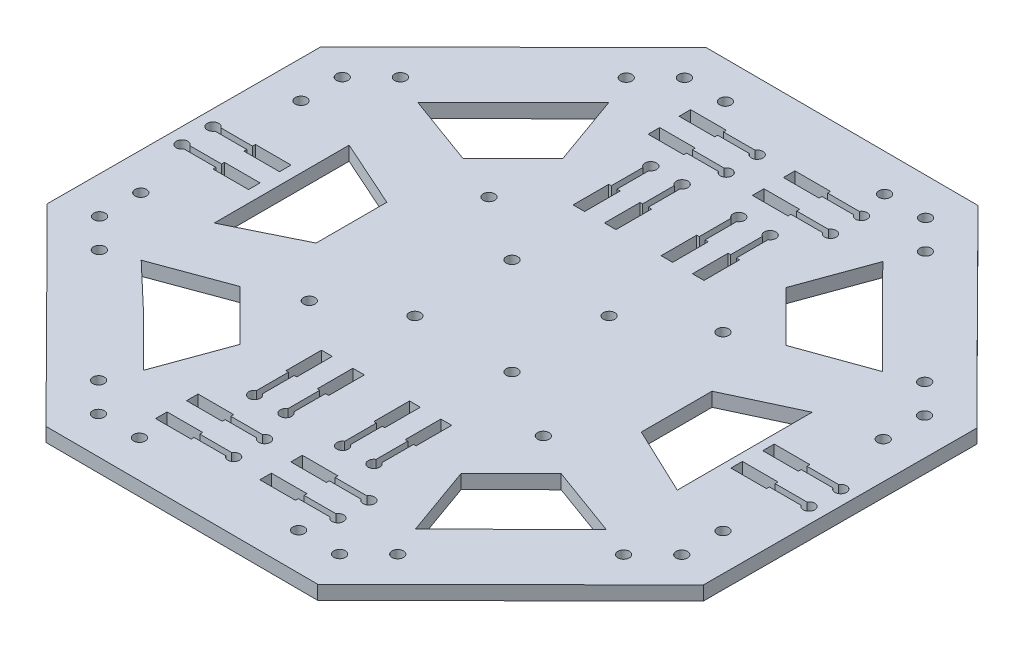
SolidWorks part; units mm, degrees
ref_plane "Front Plane" through (0, 0, 0) normal (0, 0, 1) x (1, 0, 0)
ref_plane "Top Plane" through (0, 0, 0) normal (0, 1, 0) x (1, 0, 0)
ref_plane "Right Plane" through (0, 0, 0) normal (1, 0, 0) x (0, 0, -1)
sketch "Sketch1" plane through (0, 0, 0) normal (0, 1, 0) x (1, 0, 0)
  line L1 (-101.7349, -41.757) -> (-42.4107, -101.4641)
  line L2 (-42.4107, -101.4641) -> (41.757, -101.7349)
  line L3 (41.757, -101.7349) -> (101.4641, -42.4107)
  line L4 (101.4641, -42.4107) -> (101.7349, 41.757)
  line L5 (101.7349, 41.757) -> (42.4107, 101.4641)
  line L6 (42.4107, 101.4641) -> (-41.757, 101.7349)
  line L7 (-41.757, 101.7349) -> (-101.4641, 42.4107)
  line L8 (-101.4641, 42.4107) -> (-101.7349, -41.757)
  circle A0 centre (0, 0) radius 101.6 construction
extrude "Boss-Extrude1" add sketch "Sketch1" along normal blind 4.318
sketch "Sketch6" plane through (0, 4.318, 0) normal (0, 1, 0) x (1, 0, 0)
  line L3 (-71.639, 42.551) -> (-56.8641, 57.2312)
  line L4 (-42.0892, 71.9113) -> (-56.8641, 57.2312)
  line L5 (71.639, -42.551) -> (56.8641, -57.2312)
  line L6 (42.0892, -71.9113) -> (56.8641, -57.2312)
  line L10 (42.6973, 71.7844) -> (57.3775, 57.0095)
  line L11 (72.0884, 42.3305) -> (57.3775, 57.0095)
  line L12 (-42.3683, -71.4575) -> (-57.0485, -56.6826)
  line L13 (-72.1494, -42.338) -> (-57.0485, -56.6826)
  line L17 (72.0884, -0.2319) -> (72.0884, 20.5959)
  line L18 (72.0884, -0.2319) -> (72.0884, -21.0601)
  line L19 (-70.8099, 20.5255) -> (-70.8099, -21.1305)
  line L20 (-42.0049, 42.276) -> (-34.2571, 49.9742)
  line L21 (-42.0049, 42.276) -> (-49.7279, 34.553)
  line L22 (-49.7279, 0.16) -> (-49.7279, 11.082)
  line L23 (-49.7279, 0.16) -> (-49.7279, -10.762)
  line L24 (-42.0934, -41.8234) -> (-34.3704, -49.5464)
  line L25 (-42.0934, -41.8234) -> (-49.8164, -34.1004)
  line L26 (42.0049, -42.276) -> (49.7527, -34.5779)
  line L27 (51.0064, -0.1641) -> (51.0064, -11.0861)
  line L28 (42.4224, 42.1503) -> (34.7242, 49.8981)
  line L29 (42.4224, 42.1503) -> (50.1205, 34.4024)
  line L30 (51.0064, -0.1641) -> (51.0064, 10.7579)
  line L31 (42.0049, -42.276) -> (34.2571, -49.9742)
  line L32 (-42.0892, 71.9113) -> (-34.2571, 49.9742)
  line L33 (-71.639, 42.551) -> (-49.7279, 34.553)
  line L34 (-70.8099, 20.5255) -> (-49.7279, 11.082)
  line L35 (-70.8099, -21.1305) -> (-49.7279, -10.762)
  line L36 (-49.8164, -34.1004) -> (-72.1494, -42.338)
  line L37 (-34.3704, -49.5464) -> (-42.3683, -71.4575)
  line L38 (42.0892, -71.9113) -> (34.2571, -49.9742)
  line L39 (71.639, -42.551) -> (49.7527, -34.5779)
  line L40 (72.0884, -21.0601) -> (51.0064, -11.0861)
  line L41 (51.0064, 10.7579) -> (72.0884, 20.5959)
  line L42 (72.0884, 42.3305) -> (50.1205, 34.4024)
  line L43 (34.7242, 49.8981) -> (42.6973, 71.7844)
  point P14 (-38.4006, -92.086)
  point P15 (38.0534, -92.3317)
  point P17 (38.4489, 92.2928)
  point P24 (-38.0051, 92.4948)
  point P25 (-92.3358, -37.8992)
  point P26 (-92.1872, 38.5548)
  point P27 (92.4109, 38.1328)
  point P28 (92.1652, -38.3212)
  point P40 (-42.0934, -41.8234)
  dimension "D3" = 76.454
  dimension "D4" = 76.454
  dimension "D9" = 76.454
  dimension "D12" = 76.454
  dimension "D15" = 76.454
  dimension "D18" = 76.454
  dimension "D20" = 76.454
  dimension "D21" = 76.454
extrude "Cut-Extrude1" cut sketch "Sketch6" against normal blind 12.7
ref_plane "Plane1" through (101.4641, 4.318, 42.4107) normal (0.7094, 0, -0.7048) x (-0.7048, 0, -0.7094)
hole_wizard "#15 (0.14) Diameter Hole1" positions "3DSketch3" profile "Sketch14" hole size "#15" standard "ANSI Inch" end condition through all
sketch3d "3DSketch3"
  line L0 (-42.4107, 4.318, 101.4641) -> (41.757, 4.318, 101.7349) construction
  line L1 (41.757, 4.318, 101.7349) -> (101.4641, 4.318, 42.4107) construction
  line L2 (101.4641, 4.318, 42.4107) -> (101.7349, 4.318, -41.757) construction
  line L3 (101.7349, 4.318, -41.757) -> (42.4107, 4.318, -101.4641) construction
  line L4 (42.4107, 4.318, -101.4641) -> (-41.757, 4.318, -101.7349) construction
  line L5 (-41.757, 4.318, -101.7349) -> (-101.4641, 4.318, -42.4107) construction
  line L6 (-101.4641, 4.318, -42.4107) -> (-101.7349, 4.318, 41.757) construction
  line L7 (-101.7349, 4.318, 41.757) -> (-42.4107, 4.318, 101.4641) construction
  point P0 (-37.6395, 4.318, 90.0494)
  point P2 (37.0594, 4.318, 90.2897)
  point P4 (90.0494, 4.318, 37.6395)
  point P6 (90.2897, 4.318, -37.0594)
  point P8 (37.6395, 4.318, -90.0494)
  point P10 (-37.0594, 4.318, -90.2897)
  point P12 (-90.0494, 4.318, -37.6395)
  point P14 (-90.2897, 4.318, 37.0594)
  dimension "D1" = 11.43
  dimension "D3" = 11.43
  dimension "D2" = 11.43
  dimension "D4" = 11.43
  dimension "D5" = 11.43
  dimension "D6" = 11.43
  dimension "D7" = 11.43
  dimension "D8" = 11.43
  dimension "D9" = 11.43
  dimension "D10" = 11.43
  dimension "D11" = 11.43
  dimension "D12" = 11.43
  dimension "D13" = 11.43
  dimension "D14" = 11.43
  dimension "D15" = 11.43
  dimension "D16" = 11.43
sketch "Sketch14" plane through (-37.6395, 4.318, 90.0494) normal (1, 0, 0) x (0, 0, 1)
  line L0 (0, 0) -> (0, 4.318)
  line L1 (0, 4.318) -> (1.778, 4.318)
  line L2 (1.778, 4.318) -> (1.778, 0)
  line L5 (1.778, 0) -> (0, 0)
  line L11 (0, -6.35) -> (0, 107.95) construction
  dimension "Thru Hole Dia." = 3.556
  dimension "Thru Hole Depth" = 4.318
sketch3d "3DSketch4"
  point P0 (10.0148, 4.318, 38.2045)
ref_plane "Plane2" through (0, 4.318, 0) normal (0, 1, 0) x (1, 0, 0)
sketch "Sketch19" plane through (0, 4.318, 0) normal (0, 1, 0) x (1, 0, 0)
  line L9 (-101.4641, 42.4107) -> (-101.7349, -41.757) construction
  line L10 (-101.7349, -41.757) -> (-42.4107, -101.4641) construction
  line L11 (-42.4107, -101.4641) -> (41.757, -101.7349) construction
  line L12 (41.757, -101.7349) -> (101.4641, -42.4107) construction
  line L13 (101.4641, -42.4107) -> (101.7349, 41.757) construction
  line L14 (101.7349, 41.757) -> (42.4107, 101.4641) construction
  line L15 (42.4107, 101.4641) -> (-41.757, 101.7349) construction
  line L16 (-41.757, 101.7349) -> (-101.4641, 42.4107) construction
  circle A8 centre (-90.0494, 37.6395) radius 1.778 construction
  circle A9 centre (-90.2897, -37.0594) radius 1.778 construction
  circle A10 centre (-37.6395, -90.0494) radius 1.778 construction
  circle A11 centre (37.0594, -90.2897) radius 1.778 construction
  circle A12 centre (90.0494, -37.6395) radius 1.778 construction
  circle A13 centre (90.2897, 37.0594) radius 1.778 construction
  circle A14 centre (37.6395, 90.0494) radius 1.778 construction
  circle A15 centre (-37.0594, 90.2897) radius 1.778 construction
  point P1 (-90.2488, -24.3594)
  point P2 (-90.0902, 24.9395)
  point P10 (-81.3384, -46.0685)
  point P11 (-46.5908, -81.0403)
  point P12 (-24.9395, -90.0902)
  point P13 (24.3594, -90.2488)
  point P14 (46.0685, -81.3384)
  point P15 (81.0403, -46.5908)
  point P16 (90.0902, -24.9395)
  point P17 (90.2488, 24.3594)
  point P18 (81.3384, 46.0685)
  point P19 (46.5908, 81.0403)
  point P20 (24.9395, 90.0902)
  point P21 (-24.3594, 90.2488)
  point P22 (-81.0403, 46.5908)
  point P23 (-46.0685, 81.3384)
  dimension "D2" = 11.43
  dimension "D7" = 12.7
  dimension "D11" = 11.43
  dimension "D13" = 12.7
  dimension "D16" = 11.43
  dimension "D3" = 12.7
  dimension "D5" = 12.7
  dimension "D10" = 12.7
  dimension "D12" = 12.7
  dimension "D20" = 12.7
  dimension "D27" = 12.7
  dimension "D30" = 12.7
  dimension "D1" = 12.7
  dimension "D4" = 11.43
  dimension "D6" = 11.43
  dimension "D8" = 11.43
  dimension "D9" = 11.43
  dimension "D14" = 11.43
  dimension "D15" = 12.7
  dimension "D17" = 12.7
  dimension "D18" = 11.43
  dimension "D19" = 11.43
  dimension "D21" = 12.7
  dimension "D22" = 11.43
  dimension "D23" = 12.7
  dimension "D24" = 11.43
  dimension "D25" = 12.7
  dimension "D26" = 11.43
  dimension "D28" = 11.43
  dimension "D29" = 11.43
  dimension "D31" = 12.7
  dimension "D32" = 11.43
hole_wizard "#15 (0.14) Diameter Hole3" positions "3DSketch5" profile "Sketch20" hole size "#15" standard "ANSI Inch" end condition through all
sketch3d "3DSketch5"
  point P0 (-90.2488, 4.318, 24.3594)
  point P3 (-81.3384, 4.318, 46.0685)
  point P6 (-46.5908, 4.318, 81.0403)
  point P9 (-24.9395, 4.318, 90.0902)
  point P12 (24.3594, 4.318, 90.2488)
  point P15 (46.0685, 4.318, 81.3384)
  point P18 (81.0403, 4.318, 46.5908)
  point P21 (90.0902, 4.318, 24.9395)
  point P24 (90.2488, 4.318, -24.3594)
  point P27 (81.3384, 4.318, -46.0685)
  point P30 (46.5908, 4.318, -81.0403)
  point P33 (24.9395, 4.318, -90.0902)
  point P36 (-24.3594, 4.318, -90.2488)
  point P39 (-46.0685, 4.318, -81.3384)
  point P42 (-81.0403, 4.318, -46.5908)
  point P45 (-90.0902, 4.318, -24.9395)
sketch "Sketch20" plane through (-90.2488, 4.318, 24.3594) normal (1, 0, 0) x (0, 0, 1)
  line L0 (0, 0) -> (0, 4.318)
  line L1 (0, 4.318) -> (1.778, 4.318)
  line L2 (1.778, 4.318) -> (1.778, 0)
  line L5 (1.778, 0) -> (0, 0)
  line L11 (0, -6.35) -> (0, 107.95) construction
  dimension "Thru Hole Dia." = 3.556
  dimension "Thru Hole Depth" = 4.318
sketch "Sketch21" plane through (0, 4.318, 0) normal (0, 1, 0) x (1, 0, 0)
  point P1 (-14.986, 14.986)
  point P3 (14.986, 14.986)
  point P4 (14.986, -14.986)
  point P7 (-14.986, -14.986)
hole_wizard "#15 (0.14) Diameter Hole4" positions "3DSketch6" profile "Sketch22" hole size "#15" standard "ANSI Inch" end condition through all
sketch3d "3DSketch6"
  point P0 (-14.986, 4.318, -14.986)
  point P3 (14.986, 4.318, -14.986)
  point P6 (14.986, 4.318, 14.986)
  point P9 (-14.986, 4.318, 14.986)
sketch "Sketch22" plane through (-14.986, 4.318, -14.986) normal (1, 0, 0) x (0, 0, 1)
  line L0 (0, 0) -> (0, 4.318)
  line L1 (0, 4.318) -> (1.778, 4.318)
  line L2 (1.778, 4.318) -> (1.778, 0)
  line L5 (1.778, 0) -> (0, 0)
  line L11 (0, -6.35) -> (0, 107.95) construction
  dimension "Thru Hole Dia." = 3.556
  dimension "Thru Hole Depth" = 4.318
sketch "Sketch23" plane through (0, 4.318, 0) normal (0, 1, 0) x (1, 0, 0)
  point P0 (-35.3353, 28.2247)
  point P1 (36.9126, 28.2247)
  point P2 (36.9126, -27.2465)
  point P3 (-35.3353, -27.2465)
hole_wizard "#15 (0.14) Diameter Hole5" positions "3DSketch7" profile "Sketch24" hole size "#15" standard "ANSI Inch" end condition through all
sketch3d "3DSketch7"
  point P0 (-35.3353, 4.318, -28.2247)
  point P3 (-35.3353, 4.318, 27.2465)
  point P6 (36.9126, 4.318, 27.2465)
  point P9 (36.9126, 4.318, -28.2247)
sketch "Sketch24" plane through (-35.3353, 4.318, -28.2247) normal (1, 0, 0) x (0, 0, 1)
  line L0 (0, 0) -> (0, 4.318)
  line L1 (0, 4.318) -> (1.778, 4.318)
  line L2 (1.778, 4.318) -> (1.778, 0)
  line L5 (1.778, 0) -> (0, 0)
  line L11 (0, -6.35) -> (0, 107.95) construction
  dimension "Thru Hole Dia." = 3.556
  dimension "Thru Hole Depth" = 4.318
sketch "Sketch26" plane through (0, 4.318, 0) normal (0, 1, 0) x (1, 0, 0)
  line L16 (-10.5804, -38.5558) -> (-10.5804, -49.5558)
  line L17 (-10.5804, -49.5558) -> (-9.8004, -49.5558)
  line L20 (-8.02, -49.5558) -> (-7.02, -49.5558)
  line L21 (-7.02, -49.5558) -> (-7.02, -38.5558)
  line L22 (-7.02, -38.5558) -> (-10.5804, -38.5558)
  line L23 (-9.8004, -49.5558) -> (-9.8004, -59.3344)
  line L24 (-8.02, -49.5558) -> (-8.02, -59.3344)
  line L25 (-20.2604, -38.5558) -> (-20.2604, -49.5558)
  line L26 (-20.2604, -49.5558) -> (-19.4804, -49.5558)
  line L27 (-17.7, -49.5558) -> (-16.92, -49.5558)
  line L28 (-16.92, -49.5558) -> (-16.92, -38.5558)
  line L29 (-16.92, -38.5558) -> (-20.2604, -38.5558)
  line L30 (-19.4804, -49.5558) -> (-19.4804, -59.3344)
  line L31 (-17.7, -49.5558) -> (-17.7, -59.3344)
  line L32 (16.5913, -38.5558) -> (16.5913, -49.5558)
  line L33 (16.5913, -49.5558) -> (17.3713, -49.5558)
  line L34 (19.1517, -49.5558) -> (19.9317, -49.5558)
  line L35 (19.9317, -49.5558) -> (19.9317, -38.5558)
  line L36 (19.9317, -38.5558) -> (16.5913, -38.5558)
  line L37 (17.3713, -49.5558) -> (17.3713, -59.3344)
  line L38 (19.1517, -49.5558) -> (19.1517, -59.3344)
  line L39 (6.9116, -38.5558) -> (6.9116, -49.5558)
  line L40 (6.9116, -49.5558) -> (7.6916, -49.5558)
  line L41 (9.472, -49.5558) -> (10.252, -49.5558)
  line L42 (10.252, -49.5558) -> (10.252, -38.5558)
  line L43 (10.252, -38.5558) -> (6.9116, -38.5558)
  line L44 (7.6916, -49.5558) -> (7.6916, -59.3344)
  line L45 (9.472, -49.5558) -> (9.472, -59.3344)
  line L60 (10.4713, 39.1249) -> (10.4713, 50.1249)
  line L61 (10.4713, 50.1249) -> (9.4717, 50.1249)
  line L62 (7.6913, 50.1249) -> (6.9113, 50.1249)
  line L63 (6.9113, 50.1249) -> (6.9113, 39.1249)
  line L64 (6.9113, 39.1249) -> (10.4713, 39.1249)
  line L65 (9.4717, 50.1249) -> (9.4717, 59.9035)
  line L66 (7.6913, 50.1249) -> (7.6913, 59.9035)
  line L67 (20.1513, 39.1249) -> (20.1513, 50.1249)
  line L68 (20.1513, 50.1249) -> (19.1517, 50.1249)
  line L69 (17.3713, 50.1249) -> (16.5913, 50.1249)
  line L70 (16.5913, 50.1249) -> (16.5913, 39.1249)
  line L71 (16.5913, 39.1249) -> (20.1513, 39.1249)
  line L72 (19.1517, 50.1249) -> (19.1517, 59.9035)
  line L73 (17.3713, 50.1249) -> (17.3713, 59.9035)
  line L74 (-16.7004, 39.1249) -> (-16.7004, 50.1249)
  line L75 (-16.7004, 50.1249) -> (-17.7, 50.1249)
  line L76 (-19.4804, 50.1249) -> (-20.2604, 50.1249)
  line L77 (-20.2604, 50.1249) -> (-20.2604, 39.1249)
  line L78 (-20.2604, 39.1249) -> (-16.7004, 39.1249)
  line L79 (-17.7, 50.1249) -> (-17.7, 59.9035)
  line L80 (-19.4804, 50.1249) -> (-19.4804, 59.9035)
  line L81 (-7.0207, 39.1249) -> (-7.0207, 50.1249)
  line L82 (-7.0207, 50.1249) -> (-8.0203, 50.1249)
  line L83 (-9.8007, 50.1249) -> (-10.5807, 50.1249)
  line L84 (-10.5807, 50.1249) -> (-10.5807, 39.1249)
  line L85 (-10.5807, 39.1249) -> (-7.0207, 39.1249)
  line L86 (-8.0203, 50.1249) -> (-8.0203, 59.9035)
  line L87 (-9.8007, 50.1249) -> (-9.8007, 59.9035)
  arc A2 (-9.8004, -59.3344) -> (-8.02, -59.3344) centre (-8.9102, -60.8758) ccw
  arc A3 (-19.4804, -59.3344) -> (-17.7, -59.3344) centre (-18.5902, -60.8758) ccw
  arc A4 (17.3713, -59.3344) -> (19.1517, -59.3344) centre (18.2615, -60.8758) ccw
  arc A5 (7.6916, -59.3344) -> (9.472, -59.3344) centre (8.5818, -60.8758) ccw
  arc A8 (9.4717, 59.9035) -> (7.6913, 59.9035) centre (8.5815, 61.4449) ccw
  arc A9 (19.1517, 59.9035) -> (17.3713, 59.9035) centre (18.2615, 61.4449) ccw
  arc A10 (-17.7, 59.9035) -> (-19.4804, 59.9035) centre (-18.5902, 61.4449) ccw
  arc A11 (-8.0203, 59.9035) -> (-9.8007, 59.9035) centre (-8.9105, 61.4449) ccw
  point P54 (-18.4804, 39.1249)
  dimension "D4" = 62.61
  dimension "D2" = 62.61
  dimension "D3" = 62.61
  dimension "D5" = 1.78
  dimension "D6" = 1.78
  dimension "D7" = 1.78
  dimension "D8" = 1.78
  dimension "D9" = 1.78
  dimension "D10" = 1.78
  dimension "D11" = 1.78
  dimension "D12" = 1.78
  dimension "D1" = 62.61
  dimension "D13" = 0.78
  dimension "D14" = 0.78
  dimension "D15" = 0.78
  dimension "D16" = 11
  dimension "D17" = 11
  dimension "D18" = 11.32
  dimension "D19" = 11
  dimension "D20" = 11
  dimension "D21" = 11.32
  dimension "D22" = 0.78
  dimension "D23" = 11
  dimension "D24" = 11
  dimension "D25" = 11.32
  dimension "D26" = 11
  dimension "D27" = 11
  dimension "D28" = 11.32
  dimension "D29" = 11
  dimension "D30" = 11
  dimension "D31" = 11.32
  dimension "D32" = 11.32
  dimension "D33" = 11
  dimension "D34" = 11
  dimension "D35" = 11.32
  dimension "D36" = 11
  dimension "D37" = 11
  dimension "D38" = 11.32
  dimension "D39" = 11
  dimension "D40" = 11
  dimension "D41" = 62.9083
sketch "Sketch27" plane through (0, 4.318, 0) normal (0, 1, 0) x (1, 0, 0)
  line L0 (-27.5804, -72.9041) -> (-16.5804, -72.9041)
  line L1 (-16.5804, -72.9041) -> (-16.5804, -72.0145)
  line L2 (-16.5804, -70.2341) -> (-16.5804, -69.3441)
  line L3 (-16.5804, -69.3441) -> (-27.5804, -69.3441)
  line L4 (-27.5804, -69.3441) -> (-27.5804, -72.9041)
  line L5 (-16.5804, -72.0145) -> (-6.8018, -72.0145)
  line L6 (-16.5804, -70.2341) -> (-6.8018, -70.2341)
  line L7 (-27.5804, -82.4641) -> (-16.5804, -82.4641)
  line L8 (-16.5804, -82.4641) -> (-16.5804, -81.5745)
  line L9 (-16.5804, -79.7941) -> (-16.5804, -78.9041)
  line L10 (-16.5804, -78.9041) -> (-27.5804, -78.9041)
  line L11 (-27.5804, -78.9041) -> (-27.5804, -82.4641)
  line L12 (-16.5804, -81.5745) -> (-6.8018, -81.5745)
  line L13 (-16.5804, -79.7941) -> (-6.8018, -79.7941)
  line L14 (4.8856, -73.1749) -> (15.8856, -73.1749)
  line L15 (15.8856, -73.1749) -> (15.8856, -72.2853)
  line L16 (15.8856, -70.5049) -> (15.8856, -69.6149)
  line L17 (15.8856, -69.6149) -> (4.8856, -69.6149)
  line L18 (4.8856, -69.6149) -> (4.8856, -73.1749)
  line L19 (15.8856, -72.2853) -> (25.6642, -72.2853)
  line L20 (15.8856, -70.5049) -> (25.6642, -70.5049)
  line L21 (4.8807, -82.7349) -> (15.8807, -82.7349)
  line L22 (15.8807, -82.7349) -> (15.8807, -81.8453)
  line L23 (15.8807, -80.0649) -> (15.8807, -79.1749)
  line L24 (15.8807, -79.1749) -> (4.8807, -79.1749)
  line L25 (4.8807, -79.1749) -> (4.8807, -82.7349)
  line L26 (15.8807, -81.8453) -> (25.6593, -81.8453)
  line L27 (15.8807, -80.0649) -> (25.6593, -80.0649)
  line L28 (-74.4601, -3.3231) -> (-85.4601, -3.3231)
  line L57 (-85.4601, -3.3231) -> (-85.4601, -4.2131)
  line L58 (-85.4524, -5.9935) -> (-85.4524, -6.8835)
  line L59 (-27.5804, 79.1749) -> (-16.5804, 79.1749)
  line L60 (-16.5804, 79.1749) -> (-16.5804, 80.0645)
  line L61 (-16.5804, 81.8449) -> (-16.5804, 82.7349)
  line L62 (-16.5804, 82.7349) -> (-27.5804, 82.7349)
  line L63 (-27.5804, 82.7349) -> (-27.5804, 79.1749)
  line L64 (-16.5804, 80.0645) -> (-6.8018, 80.0645)
  line L65 (-16.5804, 81.8449) -> (-6.8018, 81.8449)
  line L66 (-27.5804, 69.6149) -> (-16.5804, 69.6149)
  line L67 (-16.5804, 69.6149) -> (-16.5804, 70.5045)
  line L68 (-16.5804, 72.2849) -> (-16.5804, 73.1749)
  line L69 (-16.5804, 73.1749) -> (-27.5804, 73.1749)
  line L70 (-27.5804, 73.1749) -> (-27.5804, 69.6149)
  line L71 (-16.5804, 70.5045) -> (-6.8018, 70.5045)
  line L72 (-16.5804, 72.2849) -> (-6.8018, 72.2849)
  line L73 (4.8856, 78.9041) -> (15.8856, 78.9041)
  line L74 (15.8856, 78.9041) -> (15.8856, 79.7937)
  line L75 (15.8856, 81.5741) -> (15.8856, 82.4641)
  line L76 (15.8856, 82.4641) -> (4.8856, 82.4641)
  line L77 (4.8856, 82.4641) -> (4.8856, 78.9041)
  line L78 (15.8856, 79.7937) -> (25.6642, 79.7937)
  line L79 (15.8856, 81.5741) -> (25.6642, 81.5741)
  line L80 (4.8807, 69.3441) -> (15.8807, 69.3441)
  line L81 (15.8807, 69.3441) -> (15.8807, 70.2337)
  line L82 (15.8807, 72.0141) -> (15.8807, 72.9041)
  line L83 (15.8807, 72.9041) -> (4.8807, 72.9041)
  line L84 (4.8807, 72.9041) -> (4.8807, 69.3441)
  line L85 (15.8807, 70.2337) -> (25.6593, 70.2337)
  line L86 (15.8807, 72.0141) -> (25.6593, 72.0141)
  line L87 (-85.4524, -6.8835) -> (-74.4601, -6.8835)
  line L88 (74.7349, 2.6743) -> (85.7349, 2.6743)
  line L89 (85.7349, 2.6743) -> (85.7349, 3.5616)
  line L90 (85.7349, 5.342) -> (85.7349, 6.232)
  line L91 (85.7349, 6.232) -> (74.7349, 6.232)
  line L92 (74.7349, 6.232) -> (74.7349, 2.6743)
  line L93 (85.7349, 3.5616) -> (95.5135, 3.5616)
  line L94 (85.7349, 5.342) -> (95.5135, 5.342)
  line L95 (74.4641, -6.8857) -> (85.4641, -6.8857)
  line L96 (85.4641, -6.8857) -> (85.4641, -5.9961)
  line L97 (85.4641, -4.2157) -> (85.4641, -3.3257)
  line L98 (85.4641, -3.3257) -> (74.4641, -3.3257)
  line L99 (74.4641, -3.3257) -> (74.4641, -6.8857)
  line L100 (85.4641, -5.9961) -> (95.2427, -5.9961)
  line L101 (85.4641, -4.2157) -> (95.2427, -4.2157)
  line L102 (-74.4601, -6.8835) -> (-74.4601, -3.3231)
  line L103 (-85.4601, -4.2131) -> (-95.2387, -4.2131)
  line L104 (-85.4524, -5.9935) -> (-95.2387, -5.9935)
  line L105 (-74.4524, 6.2347) -> (-85.4524, 6.2347)
  line L106 (-85.4524, 6.2347) -> (-85.4524, 5.3447)
  line L107 (-85.4524, 3.5643) -> (-85.4524, 2.6743)
  line L108 (-85.4524, 2.6743) -> (-74.4524, 2.6743)
  line L109 (-74.4524, 2.6743) -> (-74.4524, 6.2347)
  line L110 (-85.4524, 5.3447) -> (-95.2338, 5.3447)
  line L111 (-85.4524, 3.5643) -> (-95.2338, 3.5643)
  arc A0 (-6.8018, -72.0145) -> (-6.8018, -70.2341) centre (-5.2604, -71.1243) ccw
  arc A1 (-6.8018, -81.5745) -> (-6.8018, -79.7941) centre (-5.2604, -80.6843) ccw
  arc A2 (25.6642, -72.2853) -> (25.6642, -70.5049) centre (27.2056, -71.3951) ccw
  arc A3 (25.6593, -81.8453) -> (25.6593, -80.0649) centre (27.2007, -80.9551) ccw
  arc A8 (-6.8018, 80.0645) -> (-6.8018, 81.8449) centre (-5.2604, 80.9547) ccw
  arc A9 (-6.8018, 70.5045) -> (-6.8018, 72.2849) centre (-5.2604, 71.3947) ccw
  arc A10 (25.6642, 79.7937) -> (25.6642, 81.5741) centre (27.2056, 80.6839) ccw
  arc A11 (25.6593, 70.2337) -> (25.6593, 72.0141) centre (27.2007, 71.1239) ccw
  arc A12 (95.5135, 3.5616) -> (95.5135, 5.342) centre (97.0549, 4.4518) ccw
  arc A13 (95.2427, -5.9961) -> (95.2427, -4.2157) centre (96.7841, -5.1059) ccw
  arc A14 (-95.2387, -4.2131) -> (-95.2387, -5.9935) centre (-96.7801, -5.1033) ccw
  arc A15 (-95.2338, 5.3447) -> (-95.2338, 3.5643) centre (-96.7752, 4.4545) ccw
  point P133 (15.8807, 72.4591)
  point P134 (-16.5804, 72.7299)
  dimension "D4" = 1.78
  dimension "D2" = 1.78
  dimension "D3" = 1.78
  dimension "D5" = 1.78
  dimension "D6" = 1.78
  dimension "D1" = 1.78
  dimension "D7" = 1.78
  dimension "D8" = 1.78
  dimension "D9" = 1.78
  dimension "D10" = 1.78
  dimension "D11" = 1.78
  dimension "D12" = 1.78
  dimension "D13" = 0.89
  dimension "D14" = 0.89
  dimension "D15" = 0.89
  dimension "D16" = 0.89
  dimension "D17" = 0.89
  dimension "D18" = 0.89
  dimension "D19" = 0.89
  dimension "D20" = 0.89
  dimension "D21" = 0.89
  dimension "D22" = 0.89
  dimension "D23" = 0.89
  dimension "D24" = 0.89
  dimension "D25" = 0.89
  dimension "D26" = 0.89
  dimension "D27" = 0.8896
  dimension "D28" = 0.8896
  dimension "D29" = 0.8896
  dimension "D30" = 0.8874
  dimension "D31" = 11
  dimension "D32" = 11
  dimension "D33" = 0.8896
  dimension "D34" = 11
  dimension "D35" = 11
  dimension "D36" = 11
  dimension "D37" = 11
  dimension "D38" = 11
  dimension "D39" = 11
  dimension "D40" = 11
  dimension "D41" = 11
  dimension "D42" = 11
  dimension "D43" = 11
  dimension "D44" = 11
  dimension "D45" = 11.3228
  dimension "D46" = 11.32
  dimension "D47" = 11.32
  dimension "D48" = 11.32
  dimension "D49" = 11.32
  dimension "D50" = 11
  dimension "D51" = 11.32
  dimension "D52" = 11.32
  dimension "D53" = 11.32
  dimension "D54" = 11
  dimension "D55" = 11
  dimension "D56" = 11.32
  dimension "D57" = 11
  dimension "D58" = 11
  dimension "D59" = 11.32
  dimension "D60" = 11
  dimension "D61" = 11
  dimension "D62" = 11.32
  dimension "D63" = 11
  dimension "D64" = 11
  dimension "D65" = 11.32
extrude "Cut-Extrude2" cut sketch "Sketch27" against normal blind 10
extrude "Cut-Extrude3" cut sketch "Sketch26" against normal blind 10
